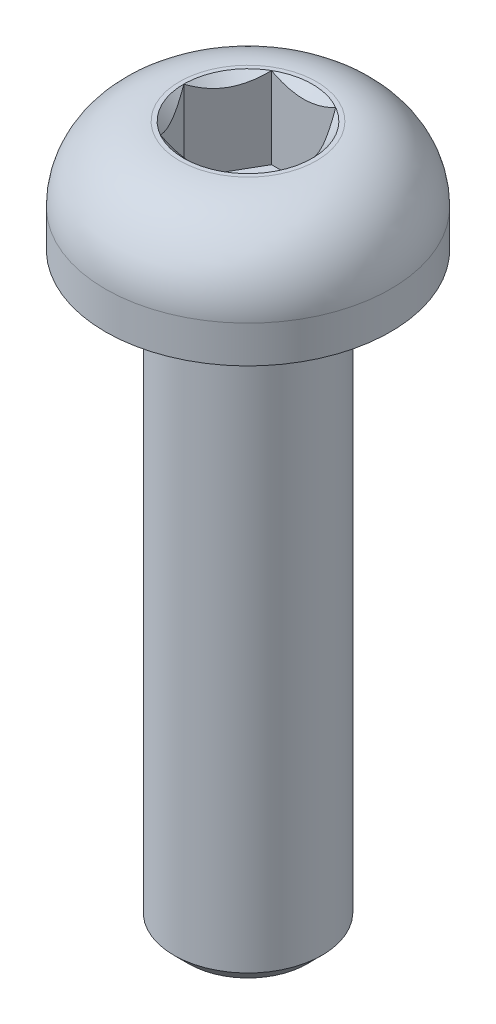
SolidWorks part; units mm, degrees
material "1023 Carbon Steel Sheet (SS)"
ref_plane "Front" through (0, 0, 0) normal (0, 0, 1) x (1, 0, 0)
ref_plane "Top" through (0, 0, 0) normal (0, 1, 0) x (1, 0, 0)
ref_plane "Right" through (0, 0, 0) normal (1, 0, 0) x (0, 0, -1)
sketch "Sketch1" plane through (0, 0, 0) normal (1, 0, 0) x (0, 0, -1)
  line L0 (0, 2.8377) -> (0, 0) construction
  line L1 (0, 0) -> (4.4824, 0) construction
  line L2 (0, -7.95) -> (0.8, -7.95)
  line L3 (0.8, -7.95) -> (1, -7.75)
  line L4 (1, -7.75) -> (1, -0.15)
  line L5 (1.15, 0) -> (1.925, 0)
  line L6 (1.925, 0) -> (1.925, 0.5)
  line L7 (0.925, 1.5) -> (0.8675, 1.5)
  line L8 (0, 0.3815) -> (0, -7.95)
  line L9 (0.75, 1.3825) -> (0.75, 0.5825)
  line L10 (0.75, 0.5825) -> (0, 0.3815)
  line L11 (0.8675, 1.5) -> (0.75, 1.3825)
  arc A0 (1, -0.15) -> (1.15, 0) centre (1.15, -0.15) cw
  arc A1 (1.925, 0.5) -> (0.925, 1.5) centre (0.925, 0.5) ccw
  dimension "D6" = 0.5
  dimension "D8" = 1.5
  dimension "D13" = 0.15
  dimension "D1" = 1.5
  dimension "D2" = 3.85
  dimension "D3" = 7.95
  dimension "D4" = 45
  dimension "D5" = 2
  dimension "D7" = 0.2
  dimension "D9" = 75
  dimension "D10" = 45
  dimension "D11" = 1.735
  dimension "D12" = 0.8
revolve "Revolve1" add sketch "Sketch1" angle 360 about L0
cosmetic thread "Cosmetic Thread1" parameters "D2"=1.548
sketch "Sketch2" plane through (0, 1.5, 0) normal (0, 1, 0) x (1, 0, 0)
  line L1 (0.433, -0.75) -> (0.866, 0)
  line L2 (0.866, 0) -> (0.433, 0.75)
  line L3 (0.433, 0.75) -> (-0.433, 0.75)
  line L4 (-0.433, 0.75) -> (-0.866, 0)
  line L5 (-0.866, 0) -> (-0.433, -0.75)
  line L6 (-0.433, -0.75) -> (0.433, -0.75)
  circle A0 centre (0, 0) radius 0.75 construction
  circle A1 centre (0, 0) radius 1.3095
  dimension "D1" = 1.5
extrude "Cut-Extrude1" cut sketch "Sketch2" against normal blind 1.1 contours L5 L6 L1 L2 L3 L4 region at (0, 1.5, 0)
extrude "Boss-Extrude1" add sketch "Sketch2<3>" against normal up to surface (0.2676 mm away) from offset 0.5 offset against normal yes
sketch "Sketch2<3>" plane through (0, 1.5, 0) normal (0, 1, 0) x (1, 0, 0) same geometry as "Sketch2"
